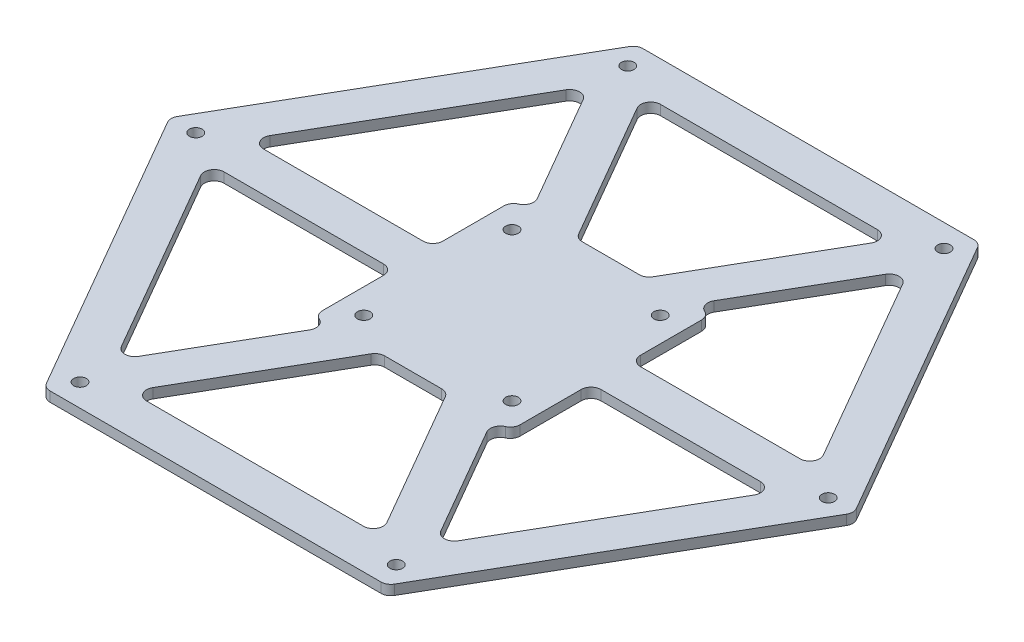
SolidWorks part; units mm, degrees
material "6061-T6 (SS)"
ref_plane "Front Plane" through (0, 0, 0) normal (0, 0, 1) x (1, 0, 0)
ref_plane "Top Plane" through (0, 0, 0) normal (0, 1, 0) x (1, 0, 0)
ref_plane "Right Plane" through (0, 0, 0) normal (1, 0, 0) x (0, 0, -1)
sketch "Sketch1" plane through (0, 0, 0) normal (0, 1, 0) x (1, 0, 0)
  line L0 (-75.0555, 130) -> (-150.1111, 0) construction
  line L7 (171.7617, 2.5) -> (88.0459, 147.5)
  line L8 (83.7158, 150) -> (-83.7158, 150)
  line L9 (-88.0459, 147.5) -> (-171.7617, 2.5)
  line L10 (-171.7617, -2.5) -> (-88.0459, -147.5)
  line L11 (-83.7158, -150) -> (83.7158, -150)
  line L12 (88.0459, -147.5) -> (171.7617, -2.5)
  line L13 (-76.4989, 112.5) -> (-8.6603, -5)
  line L14 (-59.1784, 122.5) -> (8.6603, 5)
  line L15 (-85.1592, 112.5) -> (-140.0074, 17.5)
  line L16 (-140.0074, -17.5) -> (-85.1592, -112.5)
  line L17 (-54.8483, -130) -> (54.8483, -130)
  line L18 (85.1592, -112.5) -> (140.0074, -17.5)
  line L19 (140.0074, 17.5) -> (85.1592, 112.5)
  line L20 (54.8483, 130) -> (-54.8483, 130)
  line L21 (75.0555, 130) -> (-75.0555, 130) construction
  line L22 (150.1111, 0) -> (75.0555, 130) construction
  line L23 (-150.1111, 0) -> (-75.0555, -130) construction
  line L24 (-75.0555, -130) -> (75.0555, -130) construction
  line L25 (75.0555, -130) -> (150.1111, 0) construction
  line L26 (59.1784, 122.5) -> (-8.6603, 5)
  line L27 (76.4989, 112.5) -> (8.6603, -5)
  line L28 (54.8483, 130) -> (-54.8483, 130)
  line L29 (140.0074, 17.5) -> (85.1592, 112.5)
  line L30 (135.6773, 10) -> (0, 10)
  line L31 (135.6773, -10) -> (0, -10)
  line L32 (140.0074, 17.5) -> (85.1592, 112.5)
  line L33 (85.1592, -112.5) -> (140.0074, -17.5)
  line L34 (76.4989, -112.5) -> (8.6603, 5)
  line L35 (59.1784, -122.5) -> (-8.6603, -5)
  line L36 (85.1592, -112.5) -> (140.0074, -17.5)
  line L37 (-54.8483, -130) -> (54.8483, -130)
  line L38 (-59.1784, -122.5) -> (8.6603, -5)
  line L39 (-76.4989, -112.5) -> (-8.6603, 5)
  line L40 (-54.8483, -130) -> (54.8483, -130)
  line L41 (-140.0074, -17.5) -> (-85.1592, -112.5)
  line L42 (-135.6773, -10) -> (0, -10)
  line L43 (-135.6773, 10) -> (0, 10)
  line L44 (-140.0074, -17.5) -> (-85.1592, -112.5)
  line L45 (-85.1592, 112.5) -> (-140.0074, 17.5)
  line L47 (-50, -50) -> (50, -50)
  line L48 (-50, -50) -> (-50, 50)
  line L49 (-50, 50) -> (50, 50)
  line L50 (50, -50) -> (50, 50)
  line L51 (-50, -50) -> (50, 50) construction
  line L52 (-50, 50) -> (50, -50) construction
  circle A1 centre (0, 0) radius 173.2051 construction
  circle A2 centre (-80, 138.5641) radius 3.2
  circle A3 centre (80, 138.5641) radius 3.2
  circle A4 centre (160, 0) radius 3.2
  circle A5 centre (80, -138.5641) radius 3.2
  circle A6 centre (-80, -138.5641) radius 3.2
  circle A7 centre (-160, 0) radius 3.2
  arc A8 (83.7158, -150) -> (88.0459, -147.5) centre (83.7158, -145) ccw
  arc A9 (-88.0459, -147.5) -> (-83.7158, -150) centre (-83.7158, -145) ccw
  arc A10 (-171.7617, 2.5) -> (-171.7617, -2.5) centre (-167.4316, 0) ccw
  arc A11 (171.7617, 2.5) -> (171.7617, -2.5) centre (167.4316, 0) cw
  arc A12 (88.0459, 147.5) -> (83.7158, 150) centre (83.7158, 145) ccw
  arc A13 (-83.7158, 150) -> (-88.0459, 147.5) centre (-83.7158, 145) ccw
  arc A20 (-75.0555, 130) -> (-75.0555, 130) centre (-75.0555, 130) ccw
  arc A21 (-76.4989, 112.5) -> (-85.1592, 112.5) centre (-80.829, 110) ccw
  arc A22 (-54.8483, 130) -> (-59.1784, 122.5) centre (-54.8483, 125) ccw
  arc A24 (75.0555, 130) -> (75.0555, 130) centre (75.0555, 130) ccw construction
  arc A26 (-150.1111, 0) -> (-150.1111, 0) centre (-150.1111, 0) ccw construction
  arc A28 (-75.0555, -130) -> (-75.0555, -130) centre (-75.0555, -130) ccw construction
  arc A30 (75.0555, -130) -> (75.0555, -130) centre (75.0555, -130) ccw construction
  arc A32 (150.1111, 0) -> (150.1111, 0) centre (150.1111, 0) cw construction
  arc A33 (59.1784, 122.5) -> (54.8483, 130) centre (54.8483, 125) ccw
  arc A34 (85.1592, 112.5) -> (76.4989, 112.5) centre (80.829, 110) ccw
  arc A35 (135.6773, 10) -> (140.0074, 17.5) centre (135.6773, 15) ccw
  arc A36 (140.0074, -17.5) -> (135.6773, -10) centre (135.6773, -15) ccw
  arc A37 (76.4989, -112.5) -> (85.1592, -112.5) centre (80.829, -110) ccw
  arc A38 (54.8483, -130) -> (59.1784, -122.5) centre (54.8483, -125) ccw
  arc A39 (-59.1784, -122.5) -> (-54.8483, -130) centre (-54.8483, -125) ccw
  arc A40 (-85.1592, -112.5) -> (-76.4989, -112.5) centre (-80.829, -110) ccw
  arc A41 (-135.6773, -10) -> (-140.0074, -17.5) centre (-135.6773, -15) ccw
  arc A42 (-140.0074, 17.5) -> (-135.6773, 10) centre (-135.6773, 15) ccw
  point P5 (86.6025, -150)
  point P25 (0, 0)
  point P27 (-86.6025, -150)
  point P30 (-173.2051, 0)
  point P33 (173.2051, 0)
  point P36 (86.6025, 150)
  point P39 (-86.6025, 150)
  point P69 (0, 0)
  point P105 (0, 0)
  point P134 (0, 0)
  dimension "D2" = 6
  dimension "D3" = 5
  dimension "D4" = 5
  dimension "D5" = 5
  dimension "D1" = 300
  dimension "D10" = 100
  dimension "D11" = 100
  dimension "D6" = 20
  dimension "D9" = 6
extrude "Boss-Extrude1" add sketch "Sketch1" along normal blind 10 contours L8 A13 L9 A10 L10 A9 L11 A8 L12 A11 L7 A12 A42 L15 A21 L13 L49 L14 A22 L20 A33 L26 L27 A34 L19 A35 L30 L50 L31 A36 L18 A37 L34 L47 L35 A38 L17 A39 L38 L39 A40 L16 A41 L42 L48 L43 A2 region at (167.8607, 0, 0)
sketch "Sketch2" plane through (0, 0, 0) normal (0, 1, 0) x (1, 0, 0)
  line L1 (-50, -50) -> (50, -50)
  line L2 (-50, -50) -> (-50, 50)
  line L3 (-50, 50) -> (50, 50)
  line L4 (50, -50) -> (50, 50)
  line L5 (-50, -50) -> (50, 50) construction
  line L6 (-50, 50) -> (50, -50) construction
  point P0 (0, 0)
  dimension "D1" = 100
  dimension "D2" = 100
extrude "Boss-Extrude2" add sketch "Sketch2" along normal blind 10
fillet "Fillet1" radius 5 12 edges at (-17.3205, 5, -50) (17.3205, 5, -50) (40.4145, 5, -50) (50, 5, -10) (50, 5, 10) (40.4145, 5, 50) (-17.3205, 5, 50) (17.3205, 5, 50) (-40.4145, 5, -50) (-50, 5, -10) (-50, 5, 10) (-40.4145, 5, 50)
fillet "Fillet2" radius 5 4 edges at (-50, 5, -50) (-50, 5, 50) (50, 5, 50) (50, 5, -50)
sketch "Sketch3" plane through (0, 10, 0) normal (0, 1, 0) x (1, 0, 0)
  line L5 (-37.5, -37.5) -> (37.5, 37.5) construction
  line L6 (-37.5, 37.5) -> (37.5, -37.5) construction
  circle A0 centre (-37.5, 37.5) radius 3.2
  circle A1 centre (37.5, 37.5) radius 3.2
  circle A2 centre (37.5, -37.5) radius 3.2
  circle A3 centre (-37.5, -37.5) radius 3.2
  point P0 (0, 0)
  dimension "D1" = 75
  dimension "D2" = 75
extrude "Cut-Extrude2" cut sketch "Sketch3" against normal blind 10
sketch "Sketch6" plane through (0, 10, 0) normal (0, 1, 0) x (1, 0, 0)
  line L0 (88.0459, 147.5) -> (171.7617, 2.5)
  line L1 (88.0459, 147.5) -> (171.7617, 2.5)
  line L2 (171.7617, -2.5) -> (88.0459, -147.5)
  line L3 (171.7617, -2.5) -> (88.0459, -147.5)
  line L4 (83.7158, -150) -> (-83.7158, -150)
  line L5 (83.7158, -150) -> (-83.7158, -150)
  line L6 (-88.0459, -147.5) -> (-171.7617, -2.5)
  line L7 (-88.0459, -147.5) -> (-171.7617, -2.5)
  line L8 (-171.7617, 2.5) -> (-88.0459, 147.5)
  line L9 (-171.7617, 2.5) -> (-88.0459, 147.5)
  line L10 (-83.7158, 150) -> (83.7158, 150)
  line L11 (-83.7158, 150) -> (83.7158, 150)
  arc A0 (88.0459, 147.5) -> (83.7158, 150) centre (83.7158, 145) ccw
  arc A1 (88.0459, 147.5) -> (83.7158, 150) centre (83.7158, 145) ccw
  arc A2 (171.7617, -2.5) -> (171.7617, 2.5) centre (167.4316, 0) ccw
  arc A3 (171.7617, -2.5) -> (171.7617, 2.5) centre (167.4316, 0) ccw
  arc A4 (83.7158, -150) -> (88.0459, -147.5) centre (83.7158, -145) ccw
  arc A5 (83.7158, -150) -> (88.0459, -147.5) centre (83.7158, -145) ccw
  arc A6 (-88.0459, -147.5) -> (-83.7158, -150) centre (-83.7158, -145) ccw
  arc A7 (-88.0459, -147.5) -> (-83.7158, -150) centre (-83.7158, -145) ccw
  arc A8 (-171.7617, 2.5) -> (-171.7617, -2.5) centre (-167.4316, 0) ccw
  arc A9 (-171.7617, 2.5) -> (-171.7617, -2.5) centre (-167.4316, 0) ccw
  arc A10 (-83.7158, 150) -> (-88.0459, 147.5) centre (-83.7158, 145) ccw
  arc A11 (-83.7158, 150) -> (-88.0459, 147.5) centre (-83.7158, 145) ccw
extrude "Cut-Extrude3" cut sketch "Sketch6" against normal blind 5
